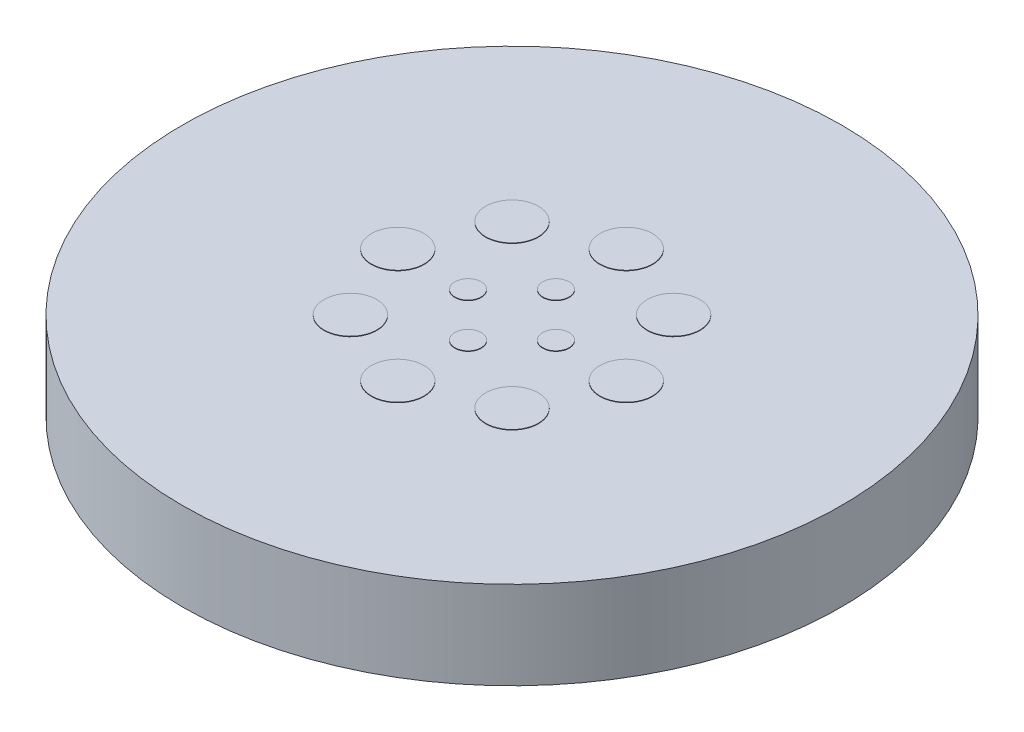
SolidWorks part; units mm, degrees
note: '?' marks a value the reader was unsure of.
ref_plane "Front Plane" through (0, 0, 0) normal (0, 0, 1) x (1, 0, 0)
ref_plane "Top Plane" through (0, 0, 0) normal (0, 1, 0) x (1, 0, 0)
ref_plane "Right Plane" through (0, 0, 0) normal (1, 0, 0) x (0, 0, -1)
sketch "Sketch1" plane through (0, 0, 0) normal (0, 1, 0) x (1, 0, 0)
  circle A1 centre (0, 0) radius 50.8
  dimension "D1" = 101.6
extrude "Boss-Extrude1" add sketch "Sketch1" along normal blind 25.4
sketch "Sketch2" plane through (0, 0, 0) normal (0, -1, 0) x (1, 0, 0)
  circle A0 centre (0, 0) radius 50.8
  circle A1 centre (0, 0) radius 69.85
  dimension "D1" = 139.7
extrude "Boss-Extrude2" add sketch "Sketch2" against normal blind 12.7
sketch "Sketch3" plane through (0, 0, 0) normal (0, -1, 0) x (1, 0, 0)
  circle A0 centre (0, 0) radius 49.53
  circle A1 centre (0, 0) radius 47.625
  dimension "D1" = 99.06
  dimension "D2" = 95.25
extrude "Cut-Extrude1" cut sketch "Sketch3" against normal blind 1.1176
sketch "Sketch4" plane through (0, 0, 0) normal (0, -1, 0) x (1, 0, 0)
  circle A0 centre (0, -59.9186) radius 3.175
  circle A1 centre (-42.3688, -42.3688) radius 3.175
  circle A2 centre (-59.9186, 0) radius 3.175
  circle A3 centre (-42.3688, 42.3688) radius 3.175
  circle A4 centre (0, 59.9186) radius 3.175
  circle A5 centre (42.3688, 42.3688) radius 3.175
  circle A6 centre (59.9186, 0) radius 3.175
  circle A7 centre (42.3688, -42.3688) radius 3.175
  point P35 (0, 0)
  dimension "D2" = 6.35
  dimension "D1" = 59.9186
  dimension "D3" = 8
extrude "Cut-Extrude2" cut sketch "Sketch4" against normal up to next
sketch "Sketch5" plane through (0, 25.4, 0) normal (0, 1, 0) x (1, 0, 0)
  circle A0 centre (0, 0) radius 11.43
  dimension "D1" = 22.86
extrude "Cut-Extrude3" cut sketch "Sketch5" against normal blind 19.05 from offset 0
sketch "Sketch30" plane through (0, 0, 0) normal (1, 0, 0) x (0, 0, -1)
  line L0 (0, -28.0613) -> (0, 0) construction
sketch "Sketch42" plane through (0, 0, 0) normal (0, -1, 0) x (1, 0, 0)
  circle A0 centre (0, 0) radius 23.8125
  dimension "D1" = 47.625
extrude "Cut-Extrude9" cut sketch "Sketch42" against normal blind 30.48 flip side to cut
sketch "Sketch43" plane through (0, 25.4, 0) normal (0, 1, 0) x (1, 0, 0)
  circle A0 centre (0, 0) radius 20.6375
extrude "Cut-Extrude10" cut sketch "Sketch43" against normal blind 19.05
sketch "Sketch52" plane through (0, 25.4, 0) normal (0, 1, 0) x (1, 0, 0)
  circle A0 centre (0, 0) radius 23.8125
  dimension "D1" = 47.625
extrude "Cut-Extrude11" cut sketch "Sketch52" against normal blind 19.05
sketch "Sketch53" plane through (0, 0, 0) normal (0, 0, 1) x (1, 0, 0)
  line L0 (0, 0) -> (0, 27.3338) construction
sketch "Sketch54" plane through (0, 0, 0) normal (0, 0, 1) x (1, 0, 0)
  line L0 (0, 0) -> (0, -18.6754)
ref_axis "Axis1" through (0, 0, 0) along (0, -1, 0)?
sketch "Sketch55" plane through (0, 0, 0) normal (0, -1, 0) x (1, 0, 0)
  circle A0 centre (8.255, 0) radius 1.905
  dimension "D1" = 3.81
  dimension "D2" = 8.255
extrude "Cut-Extrude12" cut sketch "Sketch55" against normal blind 7.62
pattern_circular "CirPattern1" count 8 over 360 about axis through (0, 0, 0) along (0, 1, 0) of "Cut-Extrude12"
sketch "Sketch58" plane through (0, 0, 0) normal (0, -1, 0) x (1, 0, 0)
  circle A0 centre (3.175, 0) radius 0.9525
  dimension "D1" = 1.905
  dimension "D2" = 3.175
extrude "Cut-Extrude14" cut sketch "Sketch58" against normal blind 7.62
pattern_circular "CirPattern2" count 4 over 360 about axis through (0, 0, 0) along (0, 1, 0) of "Cut-Extrude14"
sketch "Sketch59" plane through (0, 6.35, 0) normal (0, 1, 0) x (1, 0, 0)
  circle A0 centre (5.8372, 5.8372) radius 1.905 construction
  circle A3 centre (8.255, 0) radius 1.905 construction
  circle A5 centre (5.8372, -5.8372) radius 1.905 construction
  circle A8 centre (0, -8.255) radius 1.905 construction
  circle A12 centre (-5.8372, -5.8372) radius 1.905 construction
  circle A17 centre (-8.255, 0) radius 1.905 construction
  circle A23 centre (-5.8372, 5.8372) radius 1.905 construction
  circle A30 centre (0, 8.255) radius 1.905 construction
  circle A38 centre (0, 3.175) radius 0.9525 construction
  circle A47 centre (3.175, 0) radius 0.9525 construction
  circle A57 centre (0, -3.175) radius 0.9525 construction
  circle A68 centre (-3.175, 0) radius 0.9525 construction
  circle A104 centre (0, -3.175) radius 0.9525
  circle A105 centre (-3.175, 0) radius 0.9525
  circle A106 centre (0, 3.175) radius 0.9525
  circle A107 centre (3.175, 0) radius 0.9525
  circle A108 centre (0, 8.255) radius 1.905
  circle A109 centre (-5.8372, 5.8372) radius 1.905
  circle A110 centre (-8.255, 0) radius 1.905
  circle A111 centre (-5.8372, -5.8372) radius 1.905
  circle A112 centre (0, -8.255) radius 1.905
  circle A113 centre (5.8372, -5.8372) radius 1.905
  circle A114 centre (8.255, 0) radius 1.905
  circle A115 centre (5.8372, 5.8372) radius 1.905
extrude "Inlet Lid" add sketch "Sketch59" against normal mid plane 0.0635
sketch "Sketch60" plane through (0, 0, 0) normal (0, -1, 0) x (1, 0, 0)
  circle A0 centre (0, 3.175) radius 0.9525 construction
  circle A1 centre (-3.175, 0) radius 0.9525 construction
  circle A2 centre (0, -3.175) radius 0.9525 construction
  circle A3 centre (3.175, 0) radius 0.9525 construction
  circle A4 centre (5.8372, 5.8372) radius 1.905 construction
  circle A5 centre (0, 8.255) radius 1.905 construction
  circle A6 centre (-5.8372, 5.8372) radius 1.905 construction
  circle A7 centre (-8.255, 0) radius 1.905 construction
  circle A8 centre (-5.8372, -5.8372) radius 1.905 construction
  circle A9 centre (0, -8.255) radius 1.905 construction
  circle A10 centre (5.8372, -5.8372) radius 1.905 construction
  circle A11 centre (8.255, 0) radius 1.905 construction
  circle A12 centre (0, 3.175) radius 0.9525
  circle A13 centre (-3.175, 0) radius 0.9525
  circle A14 centre (0, -3.175) radius 0.9525
  circle A15 centre (3.175, 0) radius 0.9525
  circle A16 centre (5.8372, 5.8372) radius 1.905
  circle A17 centre (0, 8.255) radius 1.905
  circle A18 centre (-5.8372, 5.8372) radius 1.905
  circle A19 centre (-8.255, 0) radius 1.905
  circle A20 centre (-5.8372, -5.8372) radius 1.905
  circle A21 centre (0, -8.255) radius 1.905
  circle A22 centre (5.8372, -5.8372) radius 1.905
  circle A23 centre (8.255, 0) radius 1.905
extrude "Outlet Lid" add sketch "Sketch60" along normal mid plane 0.127
